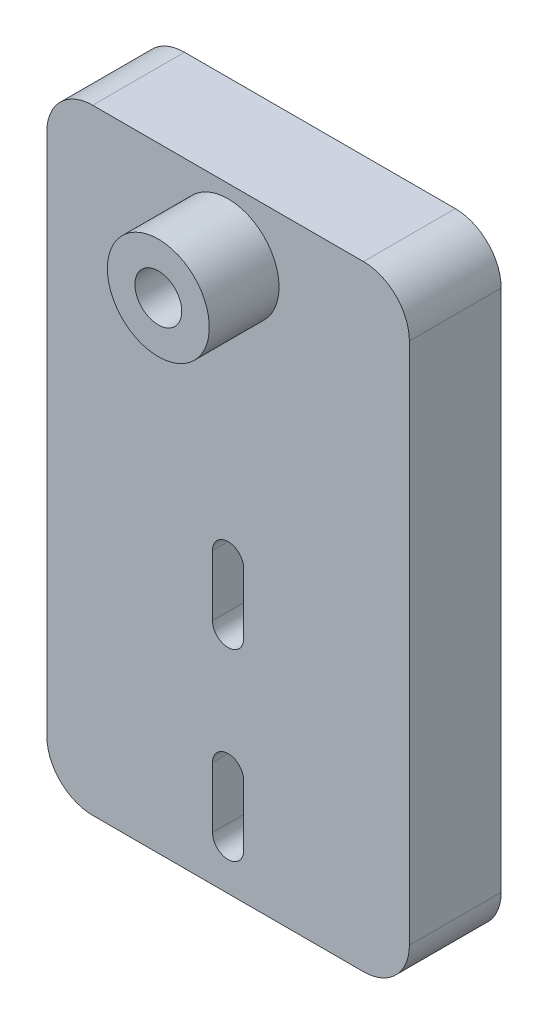
SolidWorks part; units mm, degrees
ref_plane "Front Plane" through (0, 0, 0) normal (0, 0, 1) x (1, 0, 0)
ref_plane "Top Plane" through (0, 0, 0) normal (0, 1, 0) x (1, 0, 0)
ref_plane "Right Plane" through (0, 0, 0) normal (1, 0, 0) x (0, 0, -1)
sketch "Sketch1" plane through (0, 0, 0) normal (0, 0, 1) x (1, 0, 0)
  line L0 (-19.75, 0) -> (0, 0) construction
  line L1 (14.75, -33.5) -> (-14.75, -33.5)
  line L2 (19.75, -28.5) -> (19.75, 28.5)
  line L3 (14.75, 33.5) -> (-14.75, 33.5)
  line L4 (-19.75, -28.5) -> (-19.75, 28.5)
  line L5 (0, 33.5) -> (0, 0) construction
  arc A0 (-14.75, -33.5) -> (-19.75, -28.5) centre (-14.75, -28.5) cw
  arc A1 (14.75, -33.5) -> (19.75, -28.5) centre (14.75, -28.5) ccw
  arc A2 (19.75, 28.5) -> (14.75, 33.5) centre (14.75, 28.5) ccw
  arc A3 (-14.75, 33.5) -> (-19.75, 28.5) centre (-14.75, 28.5) ccw
  circle A4 centre (0, 26.5) radius 2.55
  circle A9 centre (0, -25.29) radius 2.55 construction
  circle A10 centre (0, -5.29) radius 2.55 construction
  dimension "D2" = 5
  dimension "D3" = 7
  dimension "D5" = 20
  dimension "D4" = 5.1
  dimension "D6" = 8.21
  dimension "D1" = 67
  dimension "D9" = 39.5
extrude "Boss-Extrude1" add sketch "Sketch1" along normal blind 10
sketch "Sketch2" plane through (0, 0, 10) normal (0, 0, 1) x (1, 0, 0)
  circle A0 centre (0, 26.5) radius 5.55
  circle A1 centre (0, 26.5) radius 2.55
  circle A2 centre (0, 26.5) radius 2.55 construction
  dimension "D1" = 3
extrude "Boss-Extrude2" add sketch "Sketch2" along normal blind 7.6
sketch "Esquisse1" plane through (0, 0, 0) normal (0, 0, -1) x (-1, 0, 0)
  line L1 (2.4537, 22.25) -> (4.9075, 26.5)
  line L2 (4.9075, 26.5) -> (2.4537, 30.75)
  line L3 (2.4537, 30.75) -> (-2.4537, 30.75)
  line L4 (-2.4537, 30.75) -> (-4.9075, 26.5)
  line L5 (-4.9075, 26.5) -> (-2.4537, 22.25)
  line L6 (-2.4537, 22.25) -> (2.4537, 22.25)
  circle A0 centre (0, 26.5) radius 4.25 construction
  dimension "D1" = 8.5
extrude "Enlèv. mat.-Extru.1" cut sketch "Esquisse1" against normal blind 8
hole_wizard "Rainure de chambrage pour vis à tête ronde bombée M32" positions "Esquisse2" profile "Esquisse4" size "M3" standard "Ansi Metric" slot yes end condition through all
sketch "Esquisse2" plane through (0, 0, 0) normal (0, 0, -1) x (-1, 0, 0)
  line L0 (0, -10.29) -> (0, -0.29) construction
  point P0 (0, -5.29)
  point P3 (0, -25.29)
  dimension "D1" = 10
sketch "Esquisse4" plane through (0, -5.29, 0) normal (1, 0, 0) x (0, 1, 0)
  line L0 (0, 0) -> (0, 17.6)
  line L1 (0, 17.6) -> (1.7, 17.6)
  line L3 (1.7, 17.6) -> (1.7, 3)
  line L4 (1.7, 3) -> (3.5, 3)
  line L5 (3.5, 3) -> (3.5, 0)
  line L7 (3.5, 0) -> (0, 0)
  line L11 (0, -6.35) -> (0, 107.95) construction
  dimension "Diamètre du perçage jusqu'au prochain" = 3.4
  dimension "Profondeur du perçage jusqu'au prochain" = 17.6
  dimension "Diamètre du chambrage" = 7
  dimension "Profondeur du chambrage" = 3
